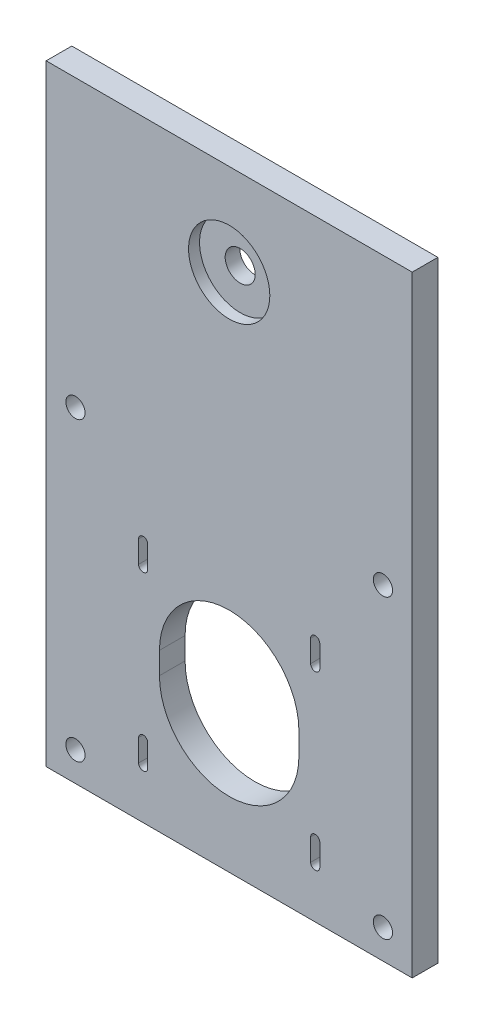
SolidWorks part; units mm, degrees
ref_plane "Front Plane" through (0, 0, 0) normal (0, 0, 1) x (1, 0, 0)
ref_plane "Top Plane" through (0, 0, 0) normal (0, 1, 0) x (1, 0, 0)
ref_plane "Right Plane" through (0, 0, 0) normal (1, 0, 0) x (0, 0, -1)
sketch "Sketch1" plane through (0, 0, 0) normal (0, 0, 1) x (1, 0, 0)
  line L1 (-50, 123.5) -> (50, 123.5)
  line L2 (-50, 123.5) -> (-50, -123.5)
  line L3 (-50, -123.5) -> (50, -123.5)
  line L4 (50, 123.5) -> (50, -123.5)
  line L5 (-50, 123.5) -> (50, -123.5) construction
  line L6 (-50, -123.5) -> (50, 123.5) construction
  line L8 (-19.05, -80.5) -> (-19.05, -86.5)
  line L9 (19.05, -86.5) -> (19.05, -80.5)
  line L10 (-23.5, -57) -> (-23.5, -63) construction
  line L14 (-22.25, -57) -> (-22.25, -63)
  line L15 (-24.75, -57) -> (-24.75, -63)
  line L16 (0, -83.5) -> (41.1398, -83.5) construction
  line L17 (0, -83.5) -> (0, -119.2312) construction
  line L18 (23.5, -57) -> (23.5, -63) construction
  line L19 (22.25, -57) -> (22.25, -63)
  line L20 (24.75, -57) -> (24.75, -63)
  line L21 (23.5, -110) -> (23.5, -104) construction
  line L22 (22.25, -110) -> (22.25, -104)
  line L23 (24.75, -110) -> (24.75, -104)
  line L24 (-23.5, -110) -> (-23.5, -104) construction
  line L25 (-22.25, -110) -> (-22.25, -104)
  line L26 (-24.75, -110) -> (-24.75, -104)
  circle A0 centre (-42, -34.5) radius 2.625
  circle A1 centre (42, -34.5) radius 2.625
  circle A2 centre (-42, -115.5) radius 2.625
  circle A3 centre (42, -115.5) radius 2.625
  arc A6 (19.05, -80.5) -> (-19.05, -80.5) centre (0, -80.5) ccw
  arc A7 (-19.05, -86.5) -> (19.05, -86.5) centre (0, -86.5) ccw
  arc A10 (-22.25, -57) -> (-24.75, -57) centre (-23.5, -57) ccw
  arc A11 (-24.75, -63) -> (-22.25, -63) centre (-23.5, -63) ccw
  arc A12 (22.25, -57) -> (24.75, -57) centre (23.5, -57) cw
  arc A13 (24.75, -63) -> (22.25, -63) centre (23.5, -63) cw
  arc A14 (22.25, -110) -> (24.75, -110) centre (23.5, -110) ccw
  arc A15 (24.75, -104) -> (22.25, -104) centre (23.5, -104) ccw
  arc A16 (-22.25, -110) -> (-24.75, -110) centre (-23.5, -110) cw
  arc A17 (-24.75, -104) -> (-22.25, -104) centre (-23.5, -104) cw
  circle A18 centre (0, 18.5) radius 4.1
  circle A19 centre (42, 115.5) radius 2.625
  circle A20 centre (-42, 115.5) radius 2.625
  circle A21 centre (-14, 32.5) radius 2.625 construction
  circle A22 centre (14, 32.5) radius 2.625 construction
  circle A23 centre (14, 4.5) radius 2.625 construction
  circle A24 centre (-14, 4.5) radius 2.625 construction
  point P0 (0, 0)
  point P14 (-23.5, -60)
  point P17 (0, -83.5)
  point P34 (23.5, -60)
  point P41 (23.5, -107)
  point P48 (-23.5, -107)
  dimension "D3" = 5.25
  dimension "D4" = 81
  dimension "D6" = 2.5
  dimension "D8" = 8
  dimension "D12" = 19.05
  dimension "D14" = 3
  dimension "D15" = 23.5
  dimension "D16" = 8.2
  dimension "D19" = 5.25
  dimension "D1" = 100
  dimension "D2" = 247
  dimension "D5" = 84
  dimension "D7" = 6
  dimension "D9" = 6
  dimension "D10" = 8
  dimension "D11" = 23.5
  dimension "D17" = 105
  dimension "D18" = 8
  dimension "D20" = 28
  dimension "D21" = 28
  dimension "D22" = 14
  dimension "D23" = 14
  dimension "D24" = 83.5
extrude "Boss-Extrude1" add sketch "Sketch1" along normal blind 7
sketch "Sketch2" plane through (0, 0, 7) normal (0, 0, 1) x (1, 0, 0)
  circle A0 centre (0, 18.5) radius 11.1
  dimension "D1" = 22.2
extrude "Cut-Extrude1" cut sketch "Sketch2" against normal blind 3
sketch "Sketch3" plane through (0, 0, 0) normal (0, 0, 1) x (1, 0, 0)
  line L0 (-23.5, -63) -> (-23.5, -57) construction
  line L1 (-25.5, -63) -> (-25.5, -57)
  line L2 (-21.5, -63) -> (-21.5, -57)
  line L3 (23.5, -63) -> (23.5, -57) construction
  line L4 (21.5, -63) -> (21.5, -57)
  line L5 (25.5, -63) -> (25.5, -57)
  line L6 (-23.5, -110) -> (-23.5, -104) construction
  line L7 (-25.5, -110) -> (-25.5, -104)
  line L8 (-21.5, -110) -> (-21.5, -104)
  line L9 (23.5, -110) -> (23.5, -104) construction
  line L10 (21.5, -110) -> (21.5, -104)
  line L11 (25.5, -110) -> (25.5, -104)
  arc A0 (-25.5, -63) -> (-21.5, -63) centre (-23.5, -63) ccw
  arc A1 (-21.5, -57) -> (-25.5, -57) centre (-23.5, -57) ccw
  arc A2 (21.5, -63) -> (25.5, -63) centre (23.5, -63) ccw
  arc A3 (25.5, -57) -> (21.5, -57) centre (23.5, -57) ccw
  arc A4 (-25.5, -110) -> (-21.5, -110) centre (-23.5, -110) ccw
  arc A5 (-21.5, -104) -> (-25.5, -104) centre (-23.5, -104) ccw
  arc A6 (21.5, -110) -> (25.5, -110) centre (23.5, -110) ccw
  arc A7 (25.5, -104) -> (21.5, -104) centre (23.5, -104) ccw
  point P4 (-23.5, -60)
  point P9 (23.5, -60)
  point P21 (-23.5, -107)
  point P29 (23.5, -107)
  dimension "D1" = 2
extrude "Cut-Extrude2" cut sketch "Sketch3" along normal blind 3
sketch "Sketch4" plane through (0, 0, 7) normal (0, 0, 1) x (1, 0, 0)
  line L0 (50, -123.5) -> (50, 123.5) construction
  line L1 (-50, 123.5) -> (50, 123.5)
  line L2 (-50, 123.5) -> (-50, 43.5)
  line L3 (-50, 43.5) -> (50, 43.5)
  line L4 (50, 123.5) -> (50, 43.5)
  line L5 (-50, 123.5) -> (50, 43.5) construction
  line L6 (-50, 43.5) -> (50, 123.5) construction
  line L7 (50, 123.5) -> (-50, 123.5) construction
  line L8 (-50, 123.5) -> (-50, -123.5) construction
  point P0 (0, 83.5)
  dimension "D1" = 80
extrude "Cut-Extrude3" cut sketch "Sketch4" against normal through all
